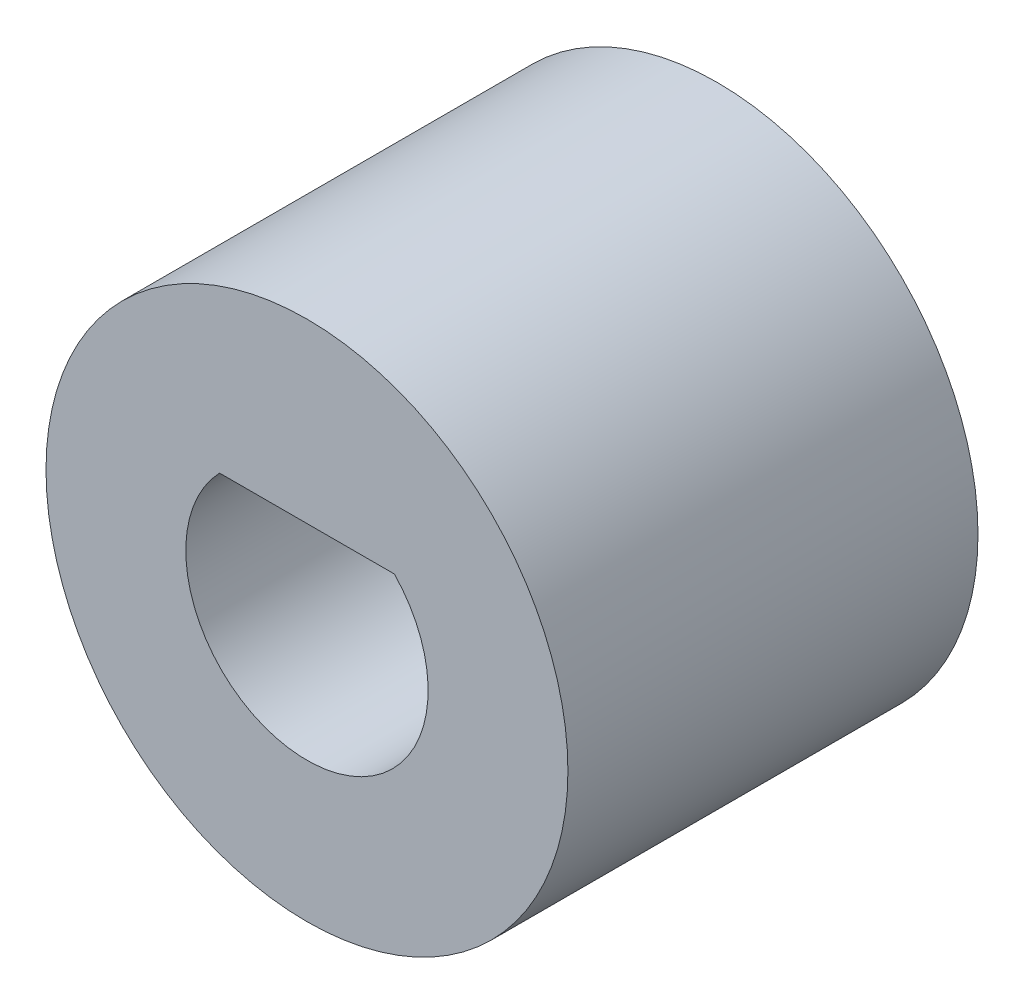
SolidWorks part; units mm, degrees
ref_plane "Plan de face" through (0, 0, 0) normal (0, 0, 1) x (1, 0, 0)
ref_plane "Plan de dessus" through (0, 0, 0) normal (0, 1, 0) x (1, 0, 0)
ref_plane "Plan de droite" through (0, 0, 0) normal (1, 0, 0) x (0, 0, -1)
sketch "Esquisse1" plane through (0, 0, 0) normal (0, 0, 1) x (1, 0, 0)
  line L0 (-2.3452, 2.25) -> (2.3452, 2.25)
  line L1 (-0.9885, -3.25) -> (1.037, -3.25) construction
  circle A0 centre (0, 0) radius 7
  arc A1 (-2.3452, 2.25) -> (2.3452, 2.25) centre (0, 0) ccw
  dimension "D1" = 14
  dimension "D2" = 6.5
  dimension "D3" = 5.5
extrude "Boss.-Extru.1" add sketch "Esquisse1" along normal blind 11
